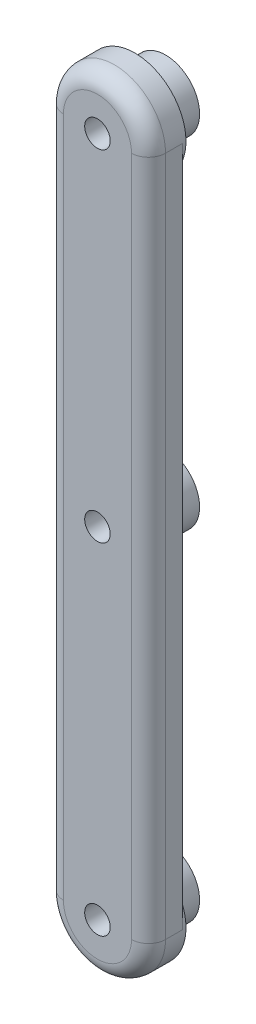
SolidWorks part; units mm, degrees
ref_plane "前视基准面" through (0, 0, 0) normal (0, 0, 1) x (1, 0, 0)
ref_plane "上视基准面" through (0, 0, 0) normal (0, 1, 0) x (1, 0, 0)
ref_plane "右视基准面" through (0, 0, 0) normal (1, 0, 0) x (0, 0, -1)
sketch "草图2" plane through (0, 0, 0) normal (0, 0, 1) x (1, 0, 0)
  line L0 (0, 40) -> (0, -40) construction
  line L1 (6, 40) -> (6, -40)
  line L2 (-6, 40) -> (-6, -40)
  arc A0 (6, 40) -> (-6, 40) centre (0, 40) ccw
  arc A1 (-6, -40) -> (6, -40) centre (0, -40) ccw
  point P3 (0, 0)
  dimension "D1" = 0
  dimension "D2" = 80
  dimension "D3" = 6
extrude "凸台-拉伸1" add sketch "草图2" along normal mid plane 4
sketch "草图3" plane through (0, 0, -2) normal (0, 0, -1) x (-1, 0, 0)
  line L1 (-6, -40) -> (-6, 40) construction
  circle A1 centre (0, -40) radius 1.5
  arc A2 (6, 40) -> (-6, 40) centre (0, 40) ccw construction
  circle A3 centre (0, 40) radius 1.5
  arc A5 (-6, -40) -> (6, -40) centre (0, -40) ccw construction
  circle A6 centre (0, -40) radius 4
  circle A7 centre (0, 40) radius 4
  circle A8 centre (0, 0) radius 1.5
  circle A9 centre (0, 0) radius 4
  circle A10 centre (0, 40) radius 6
  circle A11 centre (0, -40) radius 6
  point P9 (0, 46)
  point P14 (0, -46)
  arc M1 (6, 40) -> (-6, 40) centre (0, 40) ccw
  arc M3 (-6, -40) -> (6, -40) centre (0, -40) ccw
  dimension "D1" = 6
  dimension "D3" = 6
  dimension "D4" = 40
  dimension "D2" = 6
  dimension "D5" = 40
extrude "凸台-拉伸2" add sketch "草图3" along normal blind 4 contours A7 A3 | A9 A8 | A6 A1 region at (3.8869, -40, -2) region at (3.8869, 40, -2) region at (3.8869, 0, -2)
extrude "凸台-拉伸3" add sketch "草图3<3>" along normal blind 0.4 contours A10 A7 M1 | A11 A6 M3 region at (0, 34.1697, -2) region at (0, -45.8303, -2)
sketch "草图3<3>" plane through (0, 0, -2) normal (0, 0, -1) x (-1, 0, 0) same geometry as "草图3"
fillet "圆角1" radius 2 4 edges at (6, 0, 2) (0, -46, 2) (-6, 0, 2) (0, 46, 2)
extrude "切除-拉伸1" cut sketch "草图3<4>" against normal mid plane 10 contours A3 | A8 | A1 region at (0, -40, -2) region at (0, 40, -2) region at (0, 0, -2)
sketch "草图3<4>" plane through (0, 0, -2) normal (0, 0, -1) x (-1, 0, 0) same geometry as "草图3"
